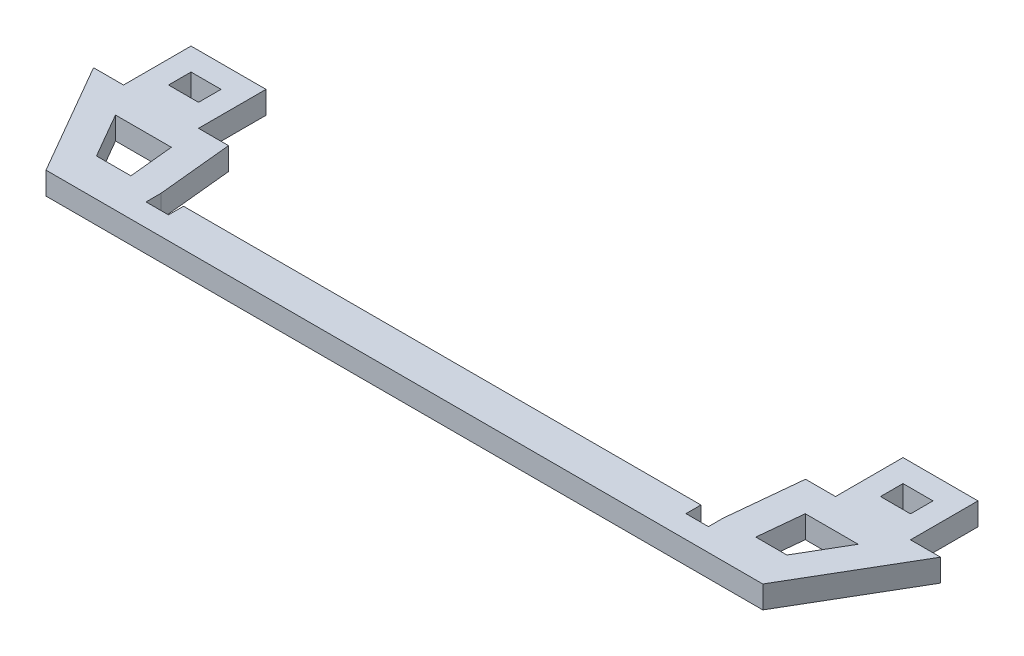
SolidWorks part; units mm, degrees
material "Custom Plastic"
ref_plane "Front Plane" through (0, 0, 0) normal (0, 0, 1) x (1, 0, 0)
ref_plane "Top Plane" through (0, 0, 0) normal (0, 1, 0) x (1, 0, 0)
ref_plane "Right Plane" through (0, 0, 0) normal (1, 0, 0) x (0, 0, -1)
sketch "Sketch1" plane through (0, 0, 0) normal (0, 1, 0) x (1, 0, 0)
  line L0 (-62.4186, -47.1587) -> (-58.4186, -47.1587)
  line L1 (-58.4186, -47.1587) -> (-58.4186, -38.1587)
  line L2 (-58.4186, -38.1587) -> (-48.4186, -38.1587)
  line L3 (-48.4186, -38.1587) -> (-48.4186, -47.1587)
  line L4 (-48.4186, -47.1587) -> (-44.4186, -47.1587)
  line L5 (-44.4186, -47.1587) -> (-43.4188, -57.1562)
  line L7 (31.5814, -57.2088) -> (32.5814, -47.2113)
  line L8 (32.5814, -47.2113) -> (36.5814, -47.2113)
  line L9 (36.5814, -47.2113) -> (36.5814, -38.2113)
  line L10 (36.5814, -38.2113) -> (46.5814, -38.2113)
  line L11 (46.5814, -38.2113) -> (46.5814, -47.2113)
  line L12 (46.5814, -47.2113) -> (50.5814, -47.2113)
  line L13 (50.5814, -47.2113) -> (41.8306, -62.1587)
  line L14 (41.8306, -62.1587) -> (-53.7583, -62.1587)
  line L15 (-53.7583, -62.1587) -> (-62.4186, -47.1587)
  line L16 (36.5478, -51.2113) -> (43.6046, -51.2113)
  line L17 (-55.4186, -41.1587) -> (-51.4186, -41.1587)
  line L18 (-55.4186, -41.1587) -> (-55.4186, -44.1587)
  line L19 (-55.4186, -44.1587) -> (-51.4186, -44.1587)
  line L20 (-51.4186, -41.1587) -> (-51.4186, -44.1587)
  line L21 (39.5814, -41.2113) -> (43.5814, -41.2113)
  line L22 (39.5814, -41.2113) -> (39.5814, -44.2113)
  line L23 (39.5814, -44.2113) -> (43.5814, -44.2113)
  line L24 (43.5814, -41.2113) -> (43.5814, -44.2113)
  line L25 (43.6046, -51.2113) -> (40.0934, -57.2088)
  line L26 (40.0934, -57.2088) -> (35.9479, -57.2088)
  line L27 (35.9479, -57.2088) -> (36.5478, -51.2113)
  line L28 (-55.4904, -51.1587) -> (-48.0385, -51.1587)
  line L29 (-48.0385, -51.1587) -> (-47.4385, -57.1587)
  line L30 (-47.4385, -57.1587) -> (-52.0263, -57.1587)
  line L31 (-52.0263, -57.1587) -> (-55.4904, -51.1587)
  line L32 (28.5814, -57.1587) -> (28.5814, -59.1587)
  line L33 (28.5814, -47.1587) -> (28.5814, -62.1587) construction
  line L34 (28.5814, -59.1587) -> (31.5814, -59.1587)
  line L35 (31.5814, -59.1587) -> (31.5814, -57.2088)
  line L36 (31.5814, -62.1587) -> (31.5814, -47.1587) construction
  line L38 (-43.4188, -57.1562) -> (-43.4188, -59.1587)
  line L39 (-43.4188, -59.1587) -> (-40.4188, -59.1587)
  line L40 (-40.4188, -59.1587) -> (-40.4188, -57.1587)
  line L41 (-40.4188, -57.1587) -> (28.5814, -57.1587)
  dimension "D1" = 15
  dimension "D2" = 4
  dimension "D3" = 9
  dimension "D4" = 3
  dimension "D5" = 3
  dimension "D7" = 120
  dimension "D8" = 10
  dimension "D9" = 85
  dimension "D10" = 3
  dimension "D11" = 3
  dimension "D12" = 3
  dimension "D13" = 3
  dimension "D14" = 3
  dimension "D15" = 3
  dimension "D17" = 4
  dimension "D18" = 4
  dimension "D19" = 4
  dimension "D20" = 4
  dimension "D21" = 4
  dimension "D23" = 2
  dimension "D24" = 3
extrude "Boss-Extrude1" add sketch "Sketch1" along normal blind 3
